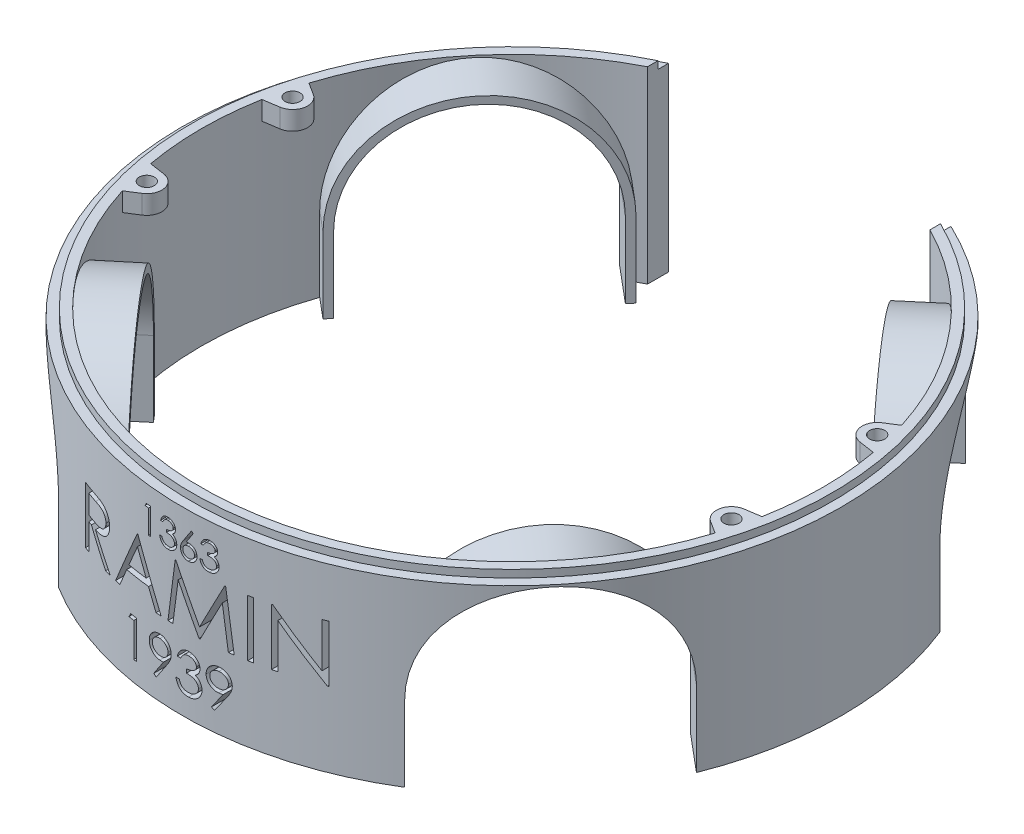
SolidWorks part; units mm, degrees
ref_plane "Front Plane" through (0, 0, 0) normal (0, 0, 1) x (1, 0, 0)
ref_plane "Top Plane" through (0, 0, 0) normal (0, 1, 0) x (1, 0, 0)
ref_plane "Right Plane" through (0, 0, 0) normal (1, 0, 0) x (0, 0, -1)
sketch "Sketch1" plane through (0, 0, 0) normal (0, 1, 0) x (1, 0, 0)
  circle A0 centre (0, 0) radius 87.5
  dimension "D1" = 175
extrude "Boss-Extrude1" add sketch "Sketch1" along normal blind 50
sketch "Sketch3" plane through (0, 50, 0) normal (0, 1, 0) x (1, 0, 0)
  line L0 (87.5, 0) -> (82.5, 0) construction
  circle A0 centre (0, 0) radius 87.5 construction
  circle A1 centre (0, 0) radius 82.5
  dimension "D1" = 5
extrude "Cut-Extrude1" cut sketch "Sketch3" against normal blind 50 contours A1 | A1 region at (0, 50, 0)
sketch "Sketch6" plane through (0, 50, 0) normal (0, 1, 0) x (1, 0, 0)
  line L0 (-37.5, 79.0569) -> (37.5, 79.0569) construction
  line L2 (-37.5, 119.3895) -> (37.5, 119.3895)
  line L3 (-37.5, 119.3895) -> (-37.5, 38.7244)
  line L4 (-37.5, 38.7244) -> (37.5, 38.7244)
  line L5 (37.5, 119.3895) -> (37.5, 38.7244)
  line L6 (-37.5, 119.3895) -> (37.5, 38.7244) construction
  line L7 (-37.5, 38.7244) -> (37.5, 119.3895) construction
  circle A1 centre (0, 0) radius 87.5 construction
  point P2 (0, 0)
  point P7 (0, 79.0569)
  circle M1 centre (0, 0) radius 82.5
  circle M2 centre (0, 0) radius 87.5
  dimension "D1" = 75
extrude "Cut-Extrude2" cut sketch "Sketch6" against normal blind 50 contours L0 M2 M1 region at (0, 50, -86.737)
sketch "Sketch7" plane through (0, 50, 0) normal (0, 1, 0) x (1, 0, 0)
  line L0 (-87.5, 0) -> (87.5, 0) construction
  line L1 (0, 0) -> (-77.6237, 19.3538) construction
  line L2 (-77.0229, 15.3991) -> (-81.1672, 14.7695)
  line L3 (-75.481, 22.7315) -> (-78.6938, 24.7695)
  line L5 (-77.6237, 21.3538) -> (-77.6237, 17.3538) construction
  circle A0 centre (-77.6237, 19.3538) radius 2
  arc A1 (-37.5, 79.0569) -> (37.5, 79.0569) centre (0, 0) ccw construction
  arc A2 (-77.0229, 15.3991) -> (-75.481, 22.7315) centre (-77.6237, 19.3538) ccw
  arc A3 (-37.5, 73.4847) -> (37.5, 73.4847) centre (0, 0) ccw construction
  arc A4 (-81.1672, 14.7695) -> (-78.6938, 24.7695) centre (0, 0) cw
  point P9 (-82.5, 0)
  point P16 (-82.3191, 5.4607)
  point P17 (-81.8752, 10.134)
  point P20 (-66.4381, 16.5649)
  point P22 (-74.5831, 35.2648)
  point P23 (-81.1672, 14.7695)
  dimension "D1" = 14
  dimension "D2" = 4
  dimension "D3" = 4
  dimension "D4" = 10
  dimension "D5" = 80
extrude "Boss-Extrude10" add sketch "Sketch7" against normal blind 5
mirror "Mirror1" about plane through (0, 0, 0) normal (1, 0, 0) of "Boss-Extrude10" second plane through (0, 0, 0) second plane normal (0, 0, 1)
sketch "Sketch8" plane through (0, 0, 0) normal (0, 0, 1) x (1, 0, 0)
  line L0 (0, 0) -> (0, 50) construction
  line L1 (-87.5, 0) -> (87.5, 0) construction
  line L2 (87.5, 50) -> (-87.5, 50) construction
ref_plane "Plane2" through (0, 0, 0) normal (0.766, 0, 0.6428) x (0, 1, 0)
sketch "Sketch9" plane through (0, 0, 0) normal (0.766, 0, 0.6428) x (0, 1, 0)
  line L0 (0, 0) -> (50, 0) construction
  line L1 (20, 27.5) -> (0, 27.5)
  line L2 (0, 82.5) -> (0, -82.5) construction
  line L3 (0, 27.5) -> (0, -27.5)
  line L4 (0, -27.5) -> (20, -27.5)
  arc A0 (20, -27.5) -> (20, 27.5) centre (20, 0) ccw
  dimension "D1" = 55
  dimension "D2" = 20
extrude "Cut-Extrude3" cut sketch "Sketch9" against normal through all
ref_plane "Plane3" through (-53.6231, 0, -44.9951) normal (0.766, 0, 0.6428) x (0, 1, 0)
sketch "Sketch10" plane through (-53.6231, 0, -44.9951) normal (0.766, 0, 0.6428) x (0, 1, 0)
  line L0 (20, -27.5) -> (0, -27.5) construction
  line L1 (0, 27.5) -> (20, 27.5) construction
  line L2 (20, -27.5) -> (0, -27.5)
  line L3 (0, 27.5) -> (20, 27.5)
  line L4 (0, 29.5) -> (20, 29.5)
  line L5 (20, -29.5) -> (0, -29.5)
  line L6 (0, 29.5) -> (0, 27.5)
  line L7 (0, -27.5) -> (0, -29.5)
  arc A0 (20, -27.5) -> (20, 27.5) centre (20, 0) ccw construction
  arc A1 (20, -27.5) -> (20, 27.5) centre (20, 0) ccw
  arc A2 (20, -29.5) -> (20, 29.5) centre (20, 0) ccw
  dimension "D1" = 2
extrude "Boss-Extrude11" add sketch "Sketch10" against normal up to next
mirror "Mirror2" about plane through (0, 0, 0) normal (0, 0, 1) of "Boss-Extrude11", "Cut-Extrude3" second plane through (0, 0, 0) second plane normal (1, 0, 0)
sketch "Sketch12" plane through (0, 50, 0) normal (0, 1, 0) x (1, 0, 0)
  line L0 (0, -87.5) -> (0, -82.5) construction
  arc A0 (-37.5, 79.0569) -> (37.5, 79.0569) centre (0, 0) ccw construction
  arc A1 (-78.6938, -24.7695) -> (78.6938, -24.7695) centre (0, 0) ccw construction
sketch "Sketch13" plane through (0, 50, 0) normal (0, 1, 0) x (1, 0, 0)
  circle A0 centre (0, 0) radius 85
  circle A1 centre (0, 0) radius 87.5
  arc A2 (-37.5, 79.0569) -> (37.5, 79.0569) centre (0, 0) ccw construction
  dimension "D1" = 2.5
extrude "Cut-Extrude4" cut sketch "Sketch13" against normal blind 2
sketch "Sketch16" plane through (0, 0, 0) normal (0, 0, 1) x (1, 0, 0)
  text T0 "RAMIN\r\n" font "Century Gothic" height 15
  text T1 "1363\r\n" font "Century Gothic" height 7
  text T2 "1939" font "Century Gothic" height 10
extrude "Cut-Extrude9" cut sketch "Sketch16" along normal blind 10000
sketch "Sketch18" plane through (0, 0, 0) normal (1, 0, 0) x (0, 0, -1)
  circle A0 centre (-21.6082, 14.2664) radius 8.8388
  circle A1 centre (0, 14.2664) radius 9.588
